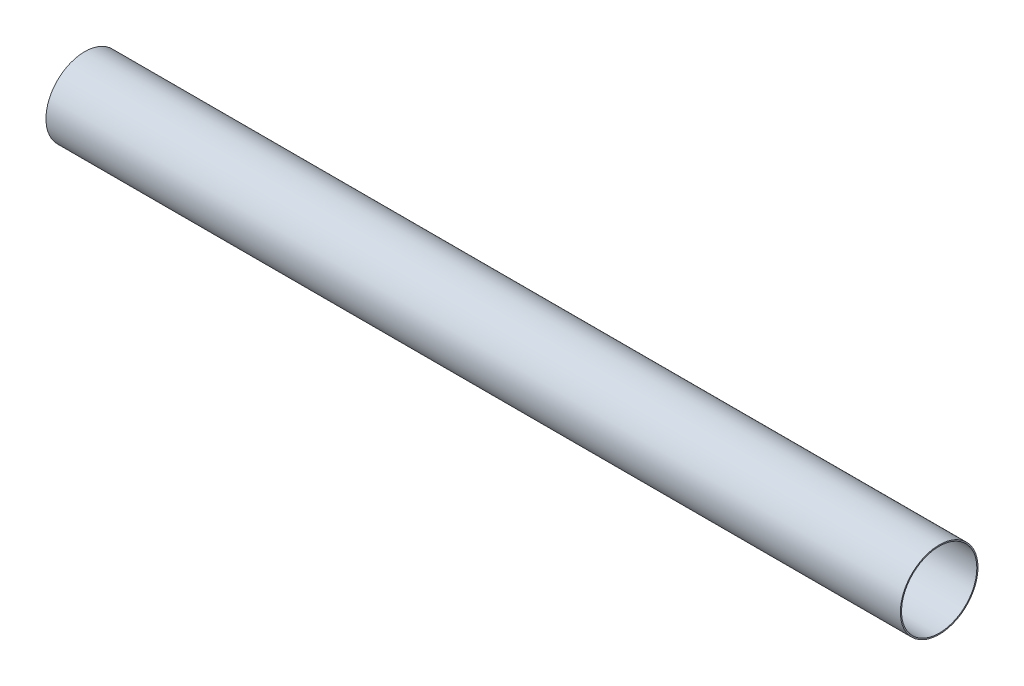
SolidWorks part; units mm, degrees
material "Natural Rubber"
ref_plane "Front Plane" through (0, 0, 0) normal (0, 0, 1) x (1, 0, 0)
ref_plane "Top Plane" through (0, 0, 0) normal (0, 1, 0) x (1, 0, 0)
ref_plane "Right Plane" through (0, 0, 0) normal (1, 0, 0) x (0, 0, -1)
sketch "Sketch1" plane through (0, 0, 0) normal (1, 0, 0) x (0, 0, -1)
  circle A0 centre (0, 0) radius 26.1937
  circle A1 centre (0, 0) radius 25.4
  dimension "D1" = 50.8
  dimension "D2" = 0.7937
extrude "Boss-Extrude1" add sketch "Sketch1" along normal mid plane 576.58
sketch "Sketch2" plane through (0, 0, 0) normal (0, 0, 1) x (1, 0, 0)
  line L0 (-288.29, 26.1938) -> (-288.29, -26.1938) construction
  line L1 (288.29, -26.1938) -> (288.29, 26.1938) construction
  circle A0 centre (-278.765, 0) radius 2.4892
  circle A1 centre (278.765, 0) radius 2.4892
  dimension "D1" = 4.9784
  dimension "D2" = 9.525
  dimension "D3" = 9.525
extrude "Cut-Extrude1" [suppressed] cut sketch "Sketch2" against normal through all both and the other way through all
sketch "Sketch3" plane through (0, 0, 0) normal (0, 1, 0) x (1, 0, 0)
  line L3 (288.29, -25.4) -> (288.29, 25.4) construction
  line L4 (-288.29, 26.1938) -> (-288.29, -26.1938) construction
  circle A0 centre (-278.765, 0) radius 2.4892
  circle A1 centre (278.765, 0) radius 2.4892
  dimension "D1" = 4.9784
  dimension "D2" = 9.525
  dimension "D3" = 9.525
extrude "Cut-Extrude2" [suppressed] cut sketch "Sketch3" against normal through all both and the other way through all
